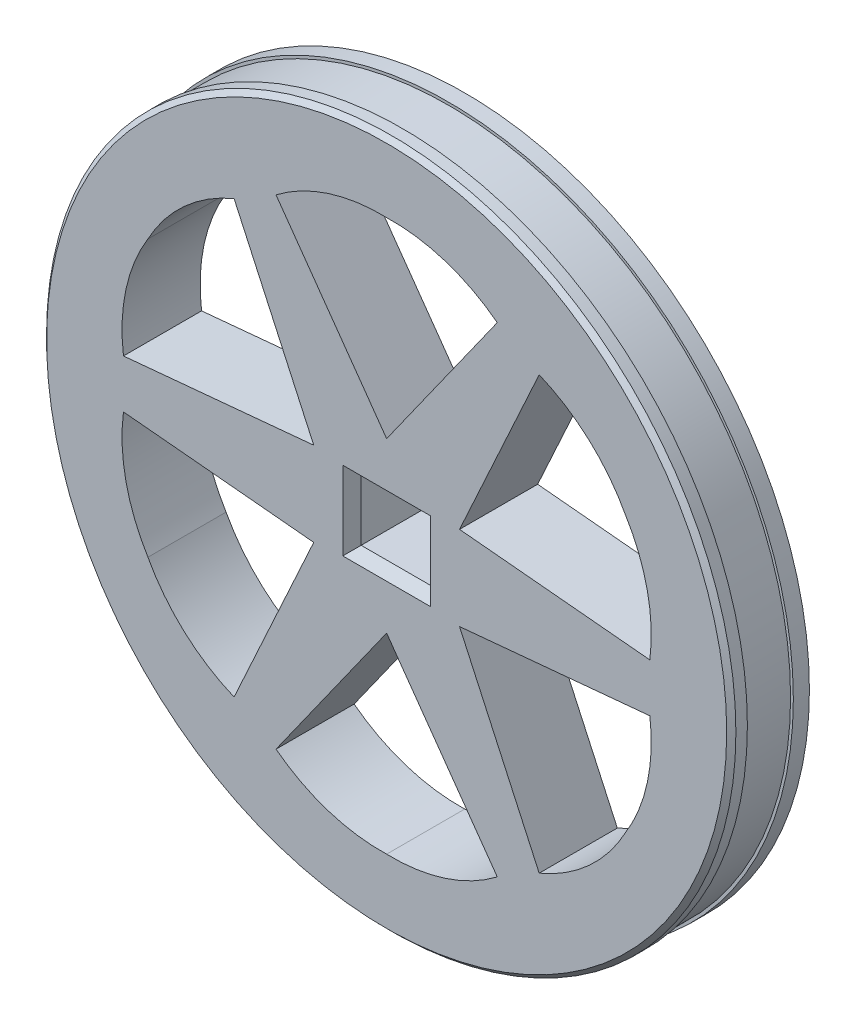
SolidWorks part; units mm, degrees
ref_plane "Front Plane" through (0, 0, 0) normal (0, 0, 1) x (1, 0, 0)
ref_plane "Top Plane" through (0, 0, 0) normal (0, 1, 0) x (1, 0, 0)
ref_plane "Right Plane" through (0, 0, 0) normal (1, 0, 0) x (0, 0, -1)
sketch "Sketch1" plane through (0, 0, 0) normal (0, 0, 1) x (1, 0, 0)
  line L1 (4.275, -3.775) -> (-4.275, -3.775)
  line L2 (4.275, -3.775) -> (4.275, 3.775)
  line L3 (4.275, 3.775) -> (-4.275, 3.775)
  line L4 (-4.275, -3.775) -> (-4.275, 3.775)
  circle A0 centre (0, 0) radius 37.5
  point P3 (0, 3.775)
  point P9 (4.275, 0)
  dimension "D1" = 75
  dimension "D2" = 8.55
  dimension "D3" = 7.55
extrude "Boss-Extrude1" add sketch "Sketch1" along normal mid plane 8.5
sketch "Sketch2" plane through (0, 0, 0) normal (0, 0, 1) x (1, 0, 0)
  line L0 (0, 0) -> (0, 32.5712) construction
  line L1 (0, 9.1586) -> (-12.0371, 26.1152)
  line L2 (0, 9.1586) -> (12.0371, 26.1152)
  arc A0 (-12.0371, 26.1152) -> (0, 29.9881) centre (-0.5568, 11.0765) cw
  arc A1 (12.0371, 26.1152) -> (0, 29.9881) centre (0.5568, 11.0765) ccw
extrude "Cut-Extrude1" cut sketch "Sketch2" along normal through all both and the other way through all
pattern_circular "CirPattern1" count 6 over 360 about axis through (0, 0, 4.25) along (0, 0, -1) of "Cut-Extrude1" reverse direction yes
sketch "Sketch3" plane through (0, 0, 0) normal (0, 0, 1) x (1, 0, 0)
  circle A0 centre (0, 0) radius 37.5
  circle A1 centre (0, 0) radius 37.2
  circle A2 centre (0, 0) radius 37.5 construction
  dimension "D1" = 0.3
extrude "Cut-Extrude2" cut sketch "Sketch3" against normal mid plane 5
chamfer "Chamfer1" distance 0.5 distance2 1.5 4 edges at (4.275, 0, 4.25) (0, 3.775, 4.25) (-4.275, 0, 4.25) (0, -3.775, 4.25) first distance on face at (37.5, 0, 4.25)
chamfer "Chamfer2" distance 0.5 angle 45 1 edges at (37.5, 0, 4.25)
